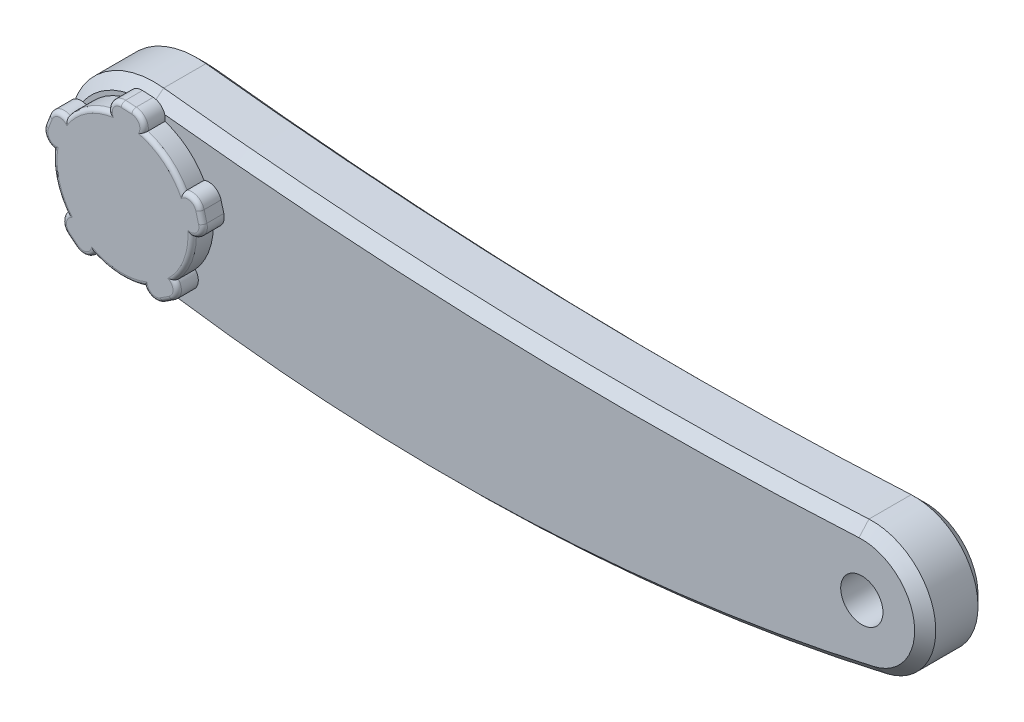
SolidWorks part; units mm, degrees
ref_plane "Front Plane" through (0, 0, 0) normal (0, 0, 1) x (1, 0, 0)
ref_plane "Top Plane" through (0, 0, 0) normal (0, 1, 0) x (1, 0, 0)
ref_plane "Right Plane" through (0, 0, 0) normal (1, 0, 0) x (0, 0, -1)
sketch "Sketch1" plane through (0, 0, 0) normal (0, 0, 1) x (1, 0, 0)
  line L0 (-61.6804, 0) -> (108.3196, 0) construction
  circle A0 centre (-61.6804, 0) radius 20
  circle A1 centre (108.3196, 0) radius 15
  arc A2 (-59.4269, 19.8726) -> (107.5057, 14.9779) centre (53.2461, 1013.5048) ccw
  arc A3 (-65.0422, -19.7154) -> (111.6893, -14.6166) centre (10.599, 423.8817) ccw
  dimension "D2" = 30
  dimension "D3" = 40
  dimension "D4" = 1000
  dimension "D5" = 450
  dimension "D1" = 170
extrude "Boss-Extrude1" add sketch "Sketch1" along normal mid plane 15 contours L0 A0 A3 A1 | A1 | A0 | A0 L0 A1 A2 region at (22.2959, 7.6812, 0) region at (-49.1463, -14.8523, 0) region at (22.8709, -12.3679, 0) region at (97.7371, 10.0231, 0)
chamfer "Chamfer1" distance 2.5 angle 45 8 edges at (-81.4822, 2.8087, -7.5) (23.5764, -25.9311, -7.5) (123.1719, 2.0996, -7.5) (23.937, 13.9344, -7.5) (123.1719, 2.0996, 7.5) (23.5764, -25.9311, 7.5) (-81.4822, 2.8087, 7.5) (23.937, 13.9344, 7.5)
sketch "Sketch2" plane through (0, 0, 7.5) normal (0, 0, 1) x (1, 0, 0)
  circle A0 centre (-61.6804, 0) radius 16.5
  dimension "D1" = 33
extrude "Boss-Extrude2" add sketch "Sketch2" along normal blind 5
sketch "Sketch3" plane through (0, 0, 12.5) normal (0, 0, 1) x (1, 0, 0)
  line L0 (-61.6804, 0) -> (-45.5901, 0)
  line L1 (-42.6923, 3.7765) -> (-43.348, 6.2235)
  line L2 (-47.7458, 8.0452) -> (-61.6804, 0)
  line L3 (-61.6804, 0) -> (-43.0201, 5) construction
  line L4 (-49.723, -10.7665) -> (-61.6804, 0)
  line L5 (-61.6804, 0) -> (-56.7082, -15.3028)
  line L6 (-52.2211, -16.8918) -> (-50.0964, -15.512)
  line L7 (-68.2249, -14.6992) -> (-61.6804, 0)
  line L8 (-61.6804, 0) -> (-74.6977, -9.4577)
  line L9 (-74.8223, -14.2161) -> (-72.8535, -15.8105)
  line L10 (-77.6826, 1.6819) -> (-61.6804, 0)
  line L11 (-61.6804, 0) -> (-74.6977, 9.4577)
  line L12 (-79.2618, 8.1057) -> (-80.1697, 5.7406)
  line L13 (-65.0258, 15.7387) -> (-61.6804, 0)
  line L14 (-61.6804, 0) -> (-56.7082, 15.3028)
  line L15 (-59.4044, 19.2257) -> (-61.9343, 19.3583)
  arc A0 (-42.6923, 3.7765) -> (-45.5901, 0) centre (-45.5901, 3) cw
  circle A1 centre (-61.6804, 0) radius 16.5
  circle A2 centre (-61.6804, 0) radius 16.5
  arc A3 (-43.348, 6.2235) -> (-47.7458, 8.0452) centre (-46.2458, 5.4471) ccw
  arc A4 (-50.0964, -15.512) -> (-49.723, -10.7665) centre (-51.7303, -12.996) ccw
  arc A5 (-52.2211, -16.8918) -> (-56.7082, -15.3028) centre (-53.855, -14.3758) cw
  arc A6 (-72.8535, -15.8105) -> (-68.2249, -14.6992) centre (-70.9656, -13.479) ccw
  arc A7 (-74.8223, -14.2161) -> (-74.6977, -9.4577) centre (-72.9344, -11.8847) cw
  arc A8 (-80.1697, 5.7406) -> (-77.6826, 1.6819) centre (-77.369, 4.6655) ccw
  arc A9 (-79.2618, 8.1057) -> (-74.6977, 9.4577) centre (-76.4611, 7.0306) cw
  arc A10 (-61.9343, 19.3583) -> (-65.0258, 15.7387) centre (-62.0913, 16.3624) ccw
  arc A11 (-59.4044, 19.2257) -> (-56.7082, 15.3028) centre (-59.5614, 16.2299) cw
  circle A12 centre (-61.6804, 0) radius 2
  point P9 (-41.6804, 0)
  point P39 (-61.6804, 0)
  circle M28 centre (-61.6804, 0) radius 16.5
  dimension "D4" = 3
  dimension "D6" = 4
  dimension "D2" = 30
  dimension "D3" = 20
  dimension "D1" = 0
  dimension "D5" = 5
extrude "Boss-Extrude3" add sketch "Sketch3" against normal blind 5 contours A11 L15 A10 M28 | A2 L3 L1 A3 | L3 A0 L1 M28 | A5 L6 A4 M28 | A7 L9 A6 M28 | A9 L12 A8 M28 region at (-45.1235, 6.4563, 12.5) region at (-44.1136, 2.6871, 12.5) region at (-52.06, -14.8141, 12.5) region at (-72.7965, -13.7273, 12.5) region at (-78.1709, 6.3301, 12.5) region at (-60.7559, 17.6395, 12.5)
fillet "Fillet1" radius 1 20 edges at (-64.2338, 18.4623, 12.5) (-60.6693, 19.292, 12.5) (-57.2111, 18.0943, 12.5) (-51.2966, 12.8229, 12.5) (-44.9107, 8.1337, 12.5) (-43.0201, 5, 12.5) (-43.0906, 1.3409, 12.5) (-46.2763, -5.9131, 12.5) (-48.7627, -13.4355, 12.5) (-51.1588, -16.2019, 12.5) (-54.6606, -17.2656, 12.5) (-62.5439, -16.4774, 12.5) (-70.4665, -16.4372, 12.5) (-73.8379, -15.0133, 12.5) (-75.9317, -12.0116, 12.5) (-77.6182, -4.2705, 12.5) (-80.0282, 3.2767, 12.5) (-79.7158, 6.9231, 12.5) (-77.508, 9.842, 12.5) (-70.6669, 13.8381, 12.5)
sketch "Sketch4" plane through (0, 0, 7.5) normal (0, 0, 1) x (1, 0, 0)
  circle A1 centre (108.3196, 0) radius 5
  dimension "D1" = 10
extrude "Cut-Extrude1" cut sketch "Sketch4" against normal blind 10
sketch "Sketch7" plane through (0, 0, -7.5) normal (0, 0, -1) x (-1, 0, 0)
  circle A0 centre (61.6804, 0) radius 5
  dimension "D1" = 10
extrude "Boss-Extrude4" add sketch "Sketch7" along normal blind 10
